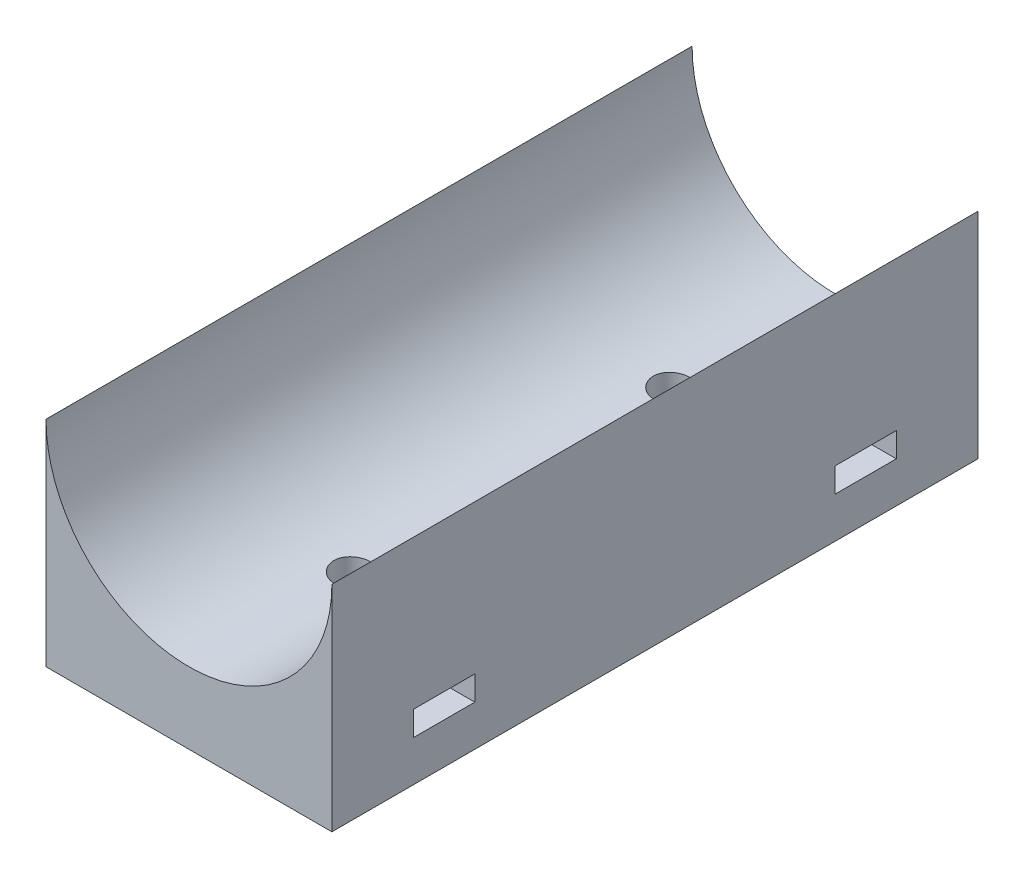
SolidWorks part; units mm, degrees
ref_plane "Plan de face" through (0, 0, 0) normal (0, 0, 1) x (1, 0, 0)
ref_plane "Plan de dessus" through (0, 0, 0) normal (0, 1, 0) x (1, 0, 0)
ref_plane "Plan de droite" through (0, 0, 0) normal (1, 0, 0) x (0, 0, -1)
sketch "Esquisse1" plane through (0, 0, 1608.5531) normal (0, 0, 1) x (1, 0, 0)
  line L0 (0, 17.5) -> (35, 17.5) construction
  line L1 (0, 0) -> (35, 0)
  line L2 (0, 26.25) -> (0, 0)
  line L6 (0, 26.25) -> (35, 26.25) construction
  line L8 (35, 26.25) -> (35, 0)
  arc A0 (0, 26.25) -> (35, 26.25) centre (17.5, 26.25) ccw
extrude "Boss.-Extru.1" add sketch "Esquisse1" along normal blind 79.1
hole_wizard "Dégagement M41" positions "Esquisse3D2" profile "Esquisse3" hole size "M4" standard "ISO"
sketch3d "Esquisse3D2"
  line L0 (0, 26.25, 1687.6531) -> (0, 26.25, 1608.5531) construction
  arc A0 (35, 26.25, 1608.5531) -> (0, 26.25, 1608.5531) centre (17.5, 26.25, 1608.5531) ccw construction
  arc A1 (35, 26.25, 1687.6531) -> (0, 26.25, 1687.6531) centre (17.5, 26.25, 1687.6531) ccw construction
  point P0 (17.5, 8.75, 1628.5531)
  point P2 (17.5, 8.75, 1667.6531)
  point P18 (17.5, 26.25, 1591.0531)
  point P22 (17.5, 26.25, 1670.1531)
  dimension "D1" = 24.7487
  dimension "D2" = 24.7487
  dimension "D3" = 26.5754
  dimension "D4" = 26.5754
sketch "Esquisse3" plane through (17.5, 8.75, 1628.5531) normal (0, 0, 1) x (-1, 0, 0)
  line L0 (0, 0) -> (0, 11.3519)
  line L1 (0, 11.3519) -> (2.25, 10)
  line L2 (2.25, 10) -> (2.25, 0)
  line L5 (2.25, 0) -> (0, 0)
  line L10 (0, 11.3519) -> (-2.25, 10) construction
  line L11 (0, -6.35) -> (0, 107.95) construction
  dimension "Diamètre du perçage" = 4.5
  dimension "Profondeur du perçage" = 10
  dimension "Angle de pointe" = 118
sketch "Esquisse7" plane through (35, 0, 0) normal (1, 0, 0) x (0, 0, -1)
  line L0 (-1687.6531, 0) -> (-1608.5531, 0) construction
  line L1 (-1677.6531, 8) -> (-1670.1531, 8)
  line L2 (-1677.6531, 8) -> (-1677.6531, 5)
  line L3 (-1677.6531, 5) -> (-1670.1531, 5)
  line L4 (-1670.1531, 8) -> (-1670.1531, 5)
  line L5 (-1626.0531, 8) -> (-1618.5531, 8)
  line L6 (-1626.0531, 8) -> (-1626.0531, 5)
  line L7 (-1626.0531, 5) -> (-1618.5531, 5)
  line L8 (-1618.5531, 8) -> (-1618.5531, 5)
  line L10 (-1687.6531, 0) -> (-1687.6531, 26.25) construction
  line L11 (-1608.5531, 0) -> (-1608.5531, 26.25) construction
  dimension "D1" = 3
  dimension "D2" = 7.5
  dimension "D3" = 7.5
  dimension "D4" = 3
  dimension "D5" = 5
  dimension "D6" = 5
  dimension "D7" = 10
  dimension "D8" = 10
extrude "Boss.-Extru.3" add sketch "Esquisse7" along direction (-1, 0, 0) on the side against the normal up to surface (35 mm away) up to face at (0, 13.125, 1648.1031)
extrude "Enlèv. mat.-Extru.5" cut sketch "Esquisse7<2>" along direction (-1, 0, 0) on the side against the normal up to surface (35 mm away) up to face at (0, 13.125, 1648.1031)
sketch "Esquisse7<2>" plane through (35, 0, 0) normal (1, 0, 0) x (0, 0, -1) same geometry as "Esquisse7"
